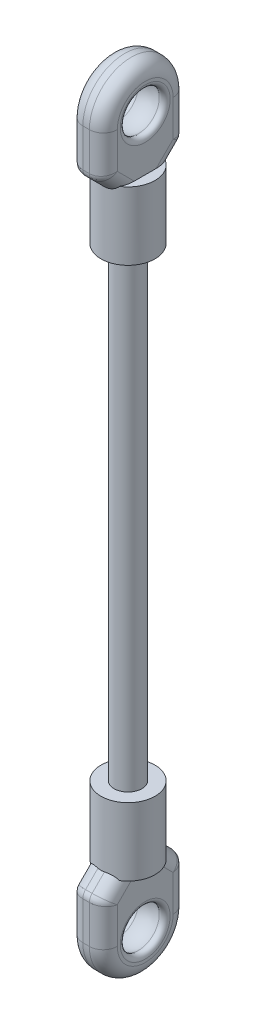
SolidWorks part; units mm, degrees
ref_plane "Front Plane" through (0, 0, 0) normal (0, 0, 1) x (1, 0, 0)
ref_plane "Top Plane" through (0, 0, 0) normal (0, 1, 0) x (1, 0, 0)
ref_plane "Right Plane" through (0, 0, 0) normal (1, 0, 0) x (0, 0, -1)
sketch "Sketch1" plane through (0, 0, 0) normal (0, 1, 0) x (1, 0, 0)
  circle A0 centre (0, 0) radius 1.5
  dimension "D1" = 3
extrude "Boss-Extrude1" add sketch "Sketch1" against normal blind 25
sketch "Sketch2" plane through (0, 0, 0) normal (0, 1, 0) x (1, 0, 0)
  circle A0 centre (0, 0) radius 2.9
extrude "Boss-Extrude2" add sketch "Sketch2" along normal blind 7.3
sketch "Sketch3" plane through (0, 0, 0) normal (1, 0, 0) x (0, 0, -1)
  line L0 (-4.5, 13) -> (-4.5, 8.5)
  line L1 (-4.5, 8.5) -> (0, 4)
  line L2 (0, 4) -> (4.5, 8.5)
  line L3 (4.5, 8.5) -> (4.5, 13)
  line L4 (-2.9, 0) -> (2.9, 0) construction
  arc A0 (4.5, 13) -> (-4.5, 13) centre (0, 13) ccw
  dimension "D1" = 9
  dimension "D2" = 13
  dimension "D3" = 8.5
extrude "Boss-Extrude3" add sketch "Sketch3" along normal mid plane 3.7
fillet "Fillet1" radius 1 2 edges at (0, 8.5, -4.5) (0, 8.5, 4.5)
fillet "Fillet2" radius 1.5 14 edges at (-1.85, 7.2202, -3.2202) (-1.85, 8.5315, -4.4239) (-1.85, 7.2202, 3.2202) (-1.85, 8.5315, 4.4239) (-1.85, 10.9571, 4.5) (-1.85, 17.5, 0) (1.85, 7.2202, -3.2202) (1.85, 8.5315, -4.4239) (1.85, 7.2202, 3.2202) (1.85, 8.5315, 4.4239) (1.85, 10.9571, 4.5) (1.85, 17.5, 0) (-1.85, 10.9571, -4.5) (1.85, 10.9571, -4.5)
sketch "Sketch4" plane through (0, 0, 0) normal (1, 0, 0) x (0, 0, -1)
  line L0 (0, 15.5) -> (0, 10.5) construction
  circle A0 centre (0, 13) radius 2.5
  dimension "D1" = 5
revolve "Cut-Revolve1" cut sketch "Sketch4" angle 360 about L0 region at (0, 13, -1.061)
fillet "Fillet3" radius 0.5 2 edges at (-1.85, 13, -1.6815) (1.85, 13, -1.6815)
mirror "Mirror1" about plane through (0, -25, 0) normal (0, 1, 0) of bodies 105
